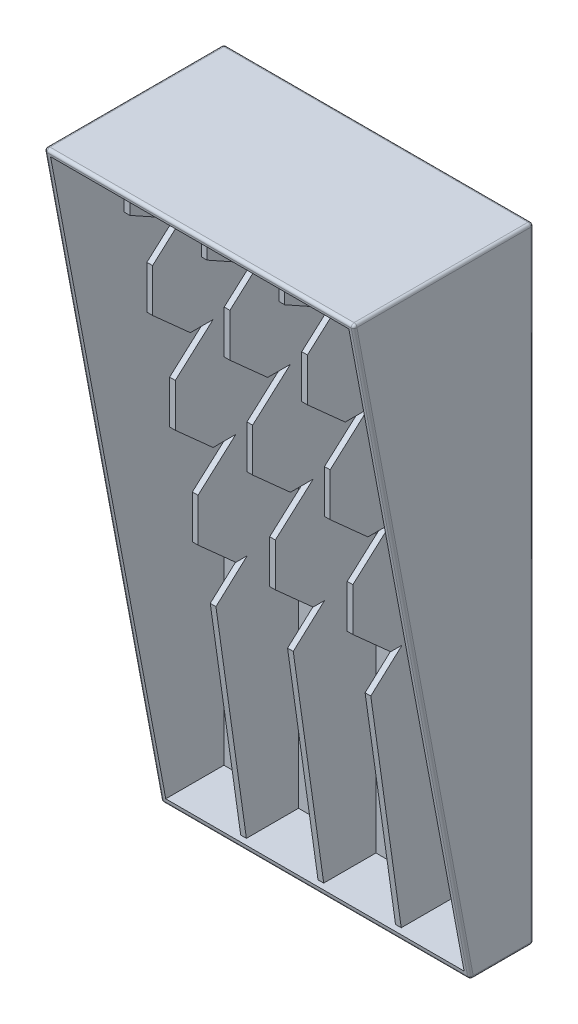
SolidWorks part; units mm, degrees
ref_plane "Front Plane" through (0, 0, 0) normal (0, 0, 1) x (1, 0, 0)
ref_plane "Top Plane" through (0, 0, 0) normal (0, 1, 0) x (1, 0, 0)
ref_plane "Right Plane" through (0, 0, 0) normal (1, 0, 0) x (0, 0, -1)
sketch "Cross Section Sketch" plane through (0, 0, 0) normal (1, 0, 0) x (0, 0, -1)
  line L0 (0, 550) -> (0, -550)
  line L1 (0, -550) -> (-110.5, -550)
  line L2 (-110.5, -550) -> (-317, 550)
  line L3 (-317, 550) -> (0, 550)
  point P2 (0, 0)
  dimension "D1" = 317
  dimension "D2" = 110.5
  dimension "D3" = 1100
extrude "Cross Section Extrude" add sketch "Cross Section Sketch" along normal blind 545
shell "Outer Shell" thickness 10 removed face at (272.5, 0, 213.75)
ref_plane "Mid Plane" through (272.5, 0, 0) normal (1, 0, 0) x (0, 0, -1)
sketch "Tall Housing Sketch" plane through (272.5, 0, 0) normal (1, 0, 0) x (0, 0, -1)
  line L0 (-100.5, -550) -> (0, -550)
  line L1 (0, -550) -> (0, 550)
  line L2 (0, 550) -> (-307, 550)
  line L3 (0, -550) -> (-110.5, -550) construction
  line L4 (-317, 550) -> (0, 550) construction
  line L5 (-307, 550) -> (-100.5, -550) construction
  line L6 (0, -110) -> (-183.1, -110) construction
  line L7 (0, 85) -> (-219.7068, 85) construction
  line L8 (0, 280) -> (-256.3136, 280) construction
  line L9 (0, 475) -> (-292.9205, 475) construction
  line L10 (-10, -110) -> (-10, 85) construction
  line L11 (-10, 85) -> (-10, 280) construction
  line L12 (-10, 280) -> (-10, 475) construction
  line L13 (-10, 475) -> (-10, 550) construction
  line L14 (-120.5, -110) -> (-187, -50.5)
  line L15 (-187, -50.5) -> (-187, 25.5)
  line L16 (-187, 25.5) -> (-120.5, 85)
  line L17 (-120.5, 85) -> (-120.5, -110) construction
  line L18 (-187, -12.5) -> (-120.5, -12.5) construction
  line L19 (-160.5, 85) -> (-160.5, 280) construction
  line L20 (-160.5, 280) -> (-227, 220.5)
  line L21 (-227, 220.5) -> (-227, 144.5)
  line L22 (-227, 144.5) -> (-160.5, 85)
  line L23 (-227, 182.5) -> (-160.5, 182.5) construction
  line L24 (-200.5, 280) -> (-200.5, 475) construction
  line L25 (-200.5, 475) -> (-267, 415.5)
  line L26 (-267, 415.5) -> (-267, 339.5)
  line L27 (-267, 339.5) -> (-200.5, 280)
  line L28 (-267, 377.5) -> (-200.5, 377.5) construction
  line L29 (-307, 550) -> (-307, 512)
  line L30 (-307, 512) -> (-240.5, 475)
  line L31 (-240.5, 475) -> (-240.5, 550) construction
  line L32 (-307, 550) -> (-240.5, 550) construction
  line L33 (-100.5, -550) -> (-155.5, -160)
  line L34 (-155.5, -160) -> (-100.5, -110)
  line L35 (-100.5, -110) -> (-100.5, -550) construction
  line L36 (-155.5, -160) -> (-100.5, -160) construction
  line L37 (-110.6747, -550) -> (-317.1747, 550) construction
  line L38 (-100.5, -110) -> (-120.5, -110)
  line L39 (-120.5, 85) -> (-160.5, 85)
  line L40 (-160.5, 280) -> (-200.5, 280)
  line L41 (-200.5, 475) -> (-240.5, 475)
  dimension "D1" = 10
  dimension "D2" = 10
  dimension "D3" = 10
  dimension "D4" = 38
  dimension "D5" = 40
  dimension "D6" = 40
  dimension "D7" = 20
  dimension "D8" = 40
  dimension "D9" = 440
  dimension "D10" = 75
  dimension "D11" = 55
  dimension "D12" = 50
  dimension "D13" = 76
  dimension "D14" = 10
extrude "Mid Divider Extrude" add sketch "Tall Housing Sketch" along normal blind 5 and the other way blind 5
ref_plane "First Plane" through (136.25, 0, 0) normal (1, 0, 0) x (0, 0, -1)
sketch "Tall Housing Copy - First Plane" plane through (136.25, 0, 0) normal (1, 0, 0) x (0, 0, -1)
  line L0 (-100.3253, -550) -> (0, -550)
  line L1 (0, -550) -> (0, 550)
  line L2 (0, 550) -> (-306.8253, 550)
  line L5 (-306.8253, 550) -> (-100.3253, -550) construction
  line L6 (0, -110) -> (-182.9253, -110) construction
  line L7 (0, 85) -> (-219.5321, 85) construction
  line L8 (0, 280) -> (-256.139, 280) construction
  line L9 (0, 475) -> (-292.7458, 475) construction
  line L10 (-10, -110) -> (-10, 85) construction
  line L11 (-10, 85) -> (-10, 280) construction
  line L12 (-10, 280) -> (-10, 475) construction
  line L13 (-10, 475) -> (-10, 550) construction
  line L14 (-120.3253, -110) -> (-186.8253, -50.5)
  line L15 (-186.8253, -50.5) -> (-186.8253, 25.5)
  line L16 (-186.8253, 25.5) -> (-120.3253, 85)
  line L17 (-120.3253, 85) -> (-120.3253, -110) construction
  line L18 (-186.8253, -12.5) -> (-120.3253, -12.5) construction
  line L19 (-160.3253, 85) -> (-160.3253, 280) construction
  line L20 (-160.3253, 280) -> (-226.8253, 220.5)
  line L21 (-226.8253, 220.5) -> (-226.8253, 144.5)
  line L22 (-226.8253, 144.5) -> (-160.3253, 85)
  line L23 (-226.8253, 182.5) -> (-160.3253, 182.5) construction
  line L24 (-200.3253, 280) -> (-200.3253, 475) construction
  line L25 (-200.3253, 475) -> (-266.8253, 415.5)
  line L26 (-266.8253, 415.5) -> (-266.8253, 339.5)
  line L27 (-266.8253, 339.5) -> (-200.3253, 280)
  line L28 (-266.8253, 377.5) -> (-200.3253, 377.5) construction
  line L29 (-306.8253, 550) -> (-306.8253, 512)
  line L30 (-306.8253, 512) -> (-240.3253, 475)
  line L31 (-240.3253, 475) -> (-240.3253, 550) construction
  line L32 (-306.8253, 550) -> (-240.3253, 550) construction
  line L33 (-100.3253, -550) -> (-155.3253, -160)
  line L34 (-155.3253, -160) -> (-100.3253, -110)
  line L35 (-100.3253, -110) -> (-100.3253, -550) construction
  line L36 (-155.3253, -160) -> (-100.3253, -160) construction
  line L37 (-110.5, -550) -> (-317, 550) construction
  line L38 (-100.3253, -110) -> (-120.3253, -110)
  line L39 (-120.3253, 85) -> (-160.3253, 85)
  line L40 (-160.3253, 280) -> (-200.3253, 280)
  line L41 (-200.3253, 475) -> (-240.3253, 475)
  dimension "D3" = 10
  dimension "D4" = 38
  dimension "D5" = 40
  dimension "D6" = 40
  dimension "D7" = 20
  dimension "D8" = 40
  dimension "D9" = 440
  dimension "D10" = 75
  dimension "D11" = 55
  dimension "D12" = 50
  dimension "D13" = 76
  dimension "D14" = 10
extrude "First Divider Extrude" add sketch "Tall Housing Copy - First Plane" along normal blind 5 and the other way blind 5
ref_plane "Third Plane" through (408.75, 0, 0) normal (1, 0, 0) x (0, 0, -1)
sketch "Tall Housing Copy - Third Plane" plane through (408.75, 0, 0) normal (1, 0, 0) x (0, 0, -1)
  line L0 (-100.3253, -550) -> (0, -550)
  line L1 (0, -550) -> (0, 550)
  line L2 (0, 550) -> (-306.8253, 550)
  line L5 (-306.8253, 550) -> (-100.3253, -550) construction
  line L6 (0, -110) -> (-182.9253, -110) construction
  line L7 (0, 85) -> (-219.5321, 85) construction
  line L8 (0, 280) -> (-256.139, 280) construction
  line L9 (0, 475) -> (-292.7458, 475) construction
  line L10 (-10, -110) -> (-10, 85) construction
  line L11 (-10, 85) -> (-10, 280) construction
  line L12 (-10, 280) -> (-10, 475) construction
  line L13 (-10, 475) -> (-10, 550) construction
  line L14 (-120.3253, -110) -> (-186.8253, -50.5)
  line L15 (-186.8253, -50.5) -> (-186.8253, 25.5)
  line L16 (-186.8253, 25.5) -> (-120.3253, 85)
  line L17 (-120.3253, 85) -> (-120.3253, -110) construction
  line L18 (-186.8253, -12.5) -> (-120.3253, -12.5) construction
  line L19 (-160.3253, 85) -> (-160.3253, 280) construction
  line L20 (-160.3253, 280) -> (-226.8253, 220.5)
  line L21 (-226.8253, 220.5) -> (-226.8253, 144.5)
  line L22 (-226.8253, 144.5) -> (-160.3253, 85)
  line L23 (-226.8253, 182.5) -> (-160.3253, 182.5) construction
  line L24 (-200.3253, 280) -> (-200.3253, 475) construction
  line L25 (-200.3253, 475) -> (-266.8253, 415.5)
  line L26 (-266.8253, 415.5) -> (-266.8253, 339.5)
  line L27 (-266.8253, 339.5) -> (-200.3253, 280)
  line L28 (-266.8253, 377.5) -> (-200.3253, 377.5) construction
  line L29 (-306.8253, 550) -> (-306.8253, 512)
  line L30 (-306.8253, 512) -> (-240.3253, 475)
  line L31 (-240.3253, 475) -> (-240.3253, 550) construction
  line L32 (-306.8253, 550) -> (-240.3253, 550) construction
  line L33 (-100.3253, -550) -> (-155.3253, -160)
  line L34 (-155.3253, -160) -> (-100.3253, -110)
  line L35 (-100.3253, -110) -> (-100.3253, -550) construction
  line L36 (-155.3253, -160) -> (-100.3253, -160) construction
  line L37 (-110.5, -550) -> (-317, 550) construction
  line L38 (-100.3253, -110) -> (-120.3253, -110)
  line L39 (-120.3253, 85) -> (-160.3253, 85)
  line L40 (-160.3253, 280) -> (-200.3253, 280)
  line L41 (-200.3253, 475) -> (-240.3253, 475)
  dimension "D3" = 10
  dimension "D4" = 38
  dimension "D5" = 40
  dimension "D6" = 40
  dimension "D7" = 20
  dimension "D8" = 40
  dimension "D9" = 440
  dimension "D10" = 75
  dimension "D11" = 55
  dimension "D12" = 50
  dimension "D13" = 76
  dimension "D14" = 10
extrude "Third Divider Extrude" add sketch "Tall Housing Copy - Third Plane" along normal blind 5 and the other way blind 5
fillet "Outer Fillet" radius 5 12 edges at (272.5, -550, 110.5) (272.5, -550, 0) (272.5, 550, 0) (272.5, 550, 317) (0, 0, 213.75) (0, -550, 55.25) (0, 0, 0) (0, 550, 158.5) (545, 0, 0) (545, -550, 55.25) (545, 0, 213.75) (545, 550, 158.5)
